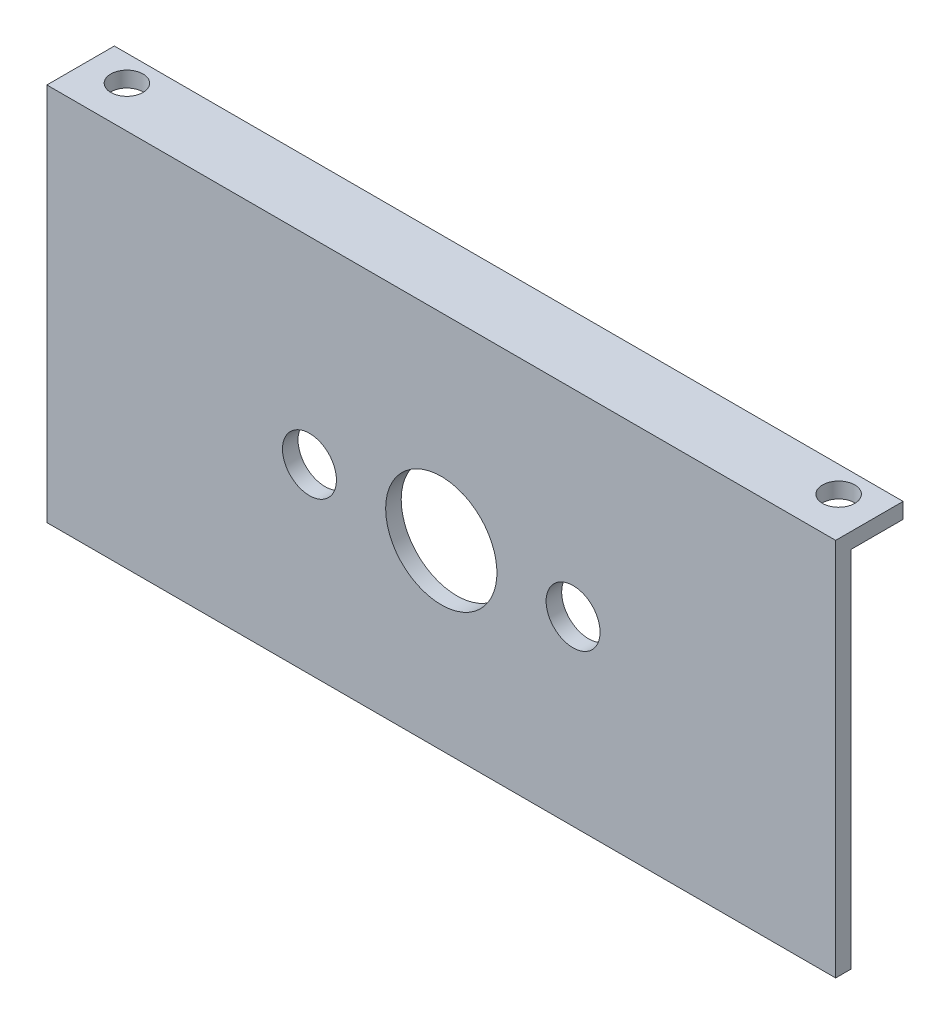
SolidWorks part; units mm, degrees
material "PTFE(普通)"
ref_plane "前视基准面" through (0, 0, 0) normal (0, 0, 1) x (1, 0, 0)
ref_plane "上视基准面" through (0, 0, 0) normal (0, 1, 0) x (1, 0, 0)
ref_plane "右视基准面" through (0, 0, 0) normal (1, 0, 0) x (0, 0, -1)
other "Configuration Table"
sketch "草图1" plane through (0, 0, 0) normal (0, 1, 0) x (1, 0, 0)
  line L1 (38, -2.5) -> (-38, -2.5)
  line L2 (38, -2.5) -> (38, 2.5)
  line L3 (38, 2.5) -> (-38, 2.5)
  line L4 (-38, -2.5) -> (-38, 2.5)
  line L5 (38, -2.5) -> (-38, 2.5) construction
  line L6 (38, 2.5) -> (-38, -2.5) construction
  circle A0 centre (-34.29, 0) radius 1.55
  circle A1 centre (34.29, 0) radius 1.55
  point P0 (0, 0)
  point P10 (0, 0)
  point P11 (0, 0)
  point P12 (0, 0)
  dimension "D3" = 3.1
  dimension "D4" = 3.1
  dimension "D1" = 34.29
  dimension "D2" = 34.29
  dimension "D5" = 38
  dimension "D6" = 2.5
extrude "凸台-拉伸1" add sketch "草图1" along normal blind 1.5 contours A1 | A0 | L4 L3 L2 L1
sketch "草图2" plane through (0, 0, 2.5) normal (0, 0, 1) x (1, 0, 0)
  line L1 (-38, 1.5) -> (38, 1.5)
  line L2 (-38, 1.5) -> (-38, 0)
  line L3 (-38, 0) -> (38, 0)
  line L4 (38, 1.5) -> (38, 0)
extrude "凸台-拉伸2" add sketch "草图2" along normal blind 1.5
sketch "草图3" plane through (0, 0, 0) normal (0, -1, 0) x (1, 0, 0)
  line L0 (38, 4) -> (38, -2.5) construction
  line L1 (-38, 4) -> (38, 4)
  line L2 (-38, 4) -> (-38, 2.5)
  line L3 (-38, 2.5) -> (38, 2.5)
  line L4 (38, 4) -> (38, 2.5)
  dimension "D1" = 1.5
extrude "凸台-拉伸3" add sketch "草图3" along normal blind 35.02
sketch "草图4" plane through (0, 0, 2.5) normal (0, 0, -1) x (-1, 0, 0)
  line L0 (-38, 0) -> (38, 0) construction
  line L1 (-38, -35.02) -> (-38, 0) construction
  circle A0 centre (0, -17.52) radius 5.36
  circle A1 centre (12.7, -17.52) radius 2.6
  circle A2 centre (-12.7, -17.52) radius 2.6
  point P12 (-49.1357, 16.0646)
  dimension "D2" = 10.72
  dimension "D5" = 5.2
  dimension "D7" = 5.2
  dimension "D1" = 17.52
  dimension "D3" = 38
  dimension "D4" = 12.7
  dimension "D8" = 12.7
extrude "切除-拉伸1" cut sketch "草图4" against normal blind 1.5
